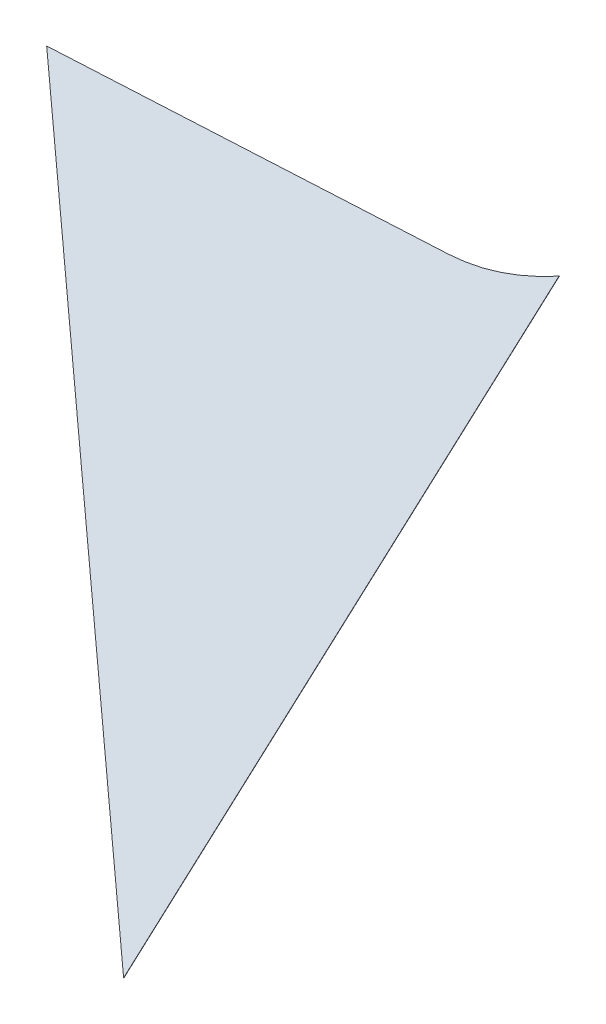
SolidWorks part; units mm, degrees
ref_plane "Front Plane" through (0, 0, 0) normal (0, 0, 1) x (1, 0, 0)
ref_plane "Top Plane" through (0, 0, 0) normal (0, 1, 0) x (1, 0, 0)
ref_plane "Right Plane" through (0, 0, 0) normal (1, 0, 0) x (0, 0, -1)
sketch "Tube Reference" plane through (-105.1856, -357.6475, -787.5535) normal (0.0455, -0.7723, -0.6336) x (0.9985, 0.0553, 0.0043)
  line L0 (-198.1326, 66.9643) -> (198.1326, 66.9643) construction
  line L1 (235, 58.2094) -> (235, 577.288) construction
  line L2 (-198.1326, 66.9643) -> (198.1326, 66.9643)
  line L3 (235, 58.2094) -> (235, 577.288)
  ellipse E0 centre (198.1326, -15.0318) end of major axis (280.1326, -15.0318) minor radius 81.9961 (263.9946, 33.8145) -> (198.1326, 66.9643) ccw construction
  ellipse E1 centre (198.1326, -15.0318) end of major axis (280.1326, -15.0318) minor radius 81.9961 (263.9946, 33.8145) -> (198.1326, 66.9643) ccw
sketch "Sketch2" plane through (-105.1856, -357.6475, -787.5535) normal (0.0455, -0.7723, -0.6336) x (0.9985, 0.0553, 0.0043)
  line L0 (-198.1326, 66.9643) -> (198.1326, 66.9643) construction
  line L1 (235, 58.2094) -> (235, 577.288) construction
  line L2 (40.5227, 66.9643) -> (198.1326, 66.9643)
  line L3 (235, 58.2094) -> (235, 287.1081)
  line L4 (235, 58.2094) -> (235, 577.288) construction
  line L5 (235, 287.1081) -> (40.5227, 66.9643)
  ellipse E0 centre (198.1326, -15.0318) end of major axis (280.1326, -15.0318) minor radius 81.9961 (263.9946, 33.8145) -> (198.1326, 66.9643) ccw construction
  ellipse E1 centre (198.1326, -15.0318) end of major axis (280.1326, -15.0318) minor radius 81.9961 (235, 58.2094) -> (198.1326, 66.9643) ccw
extrude "Boss-Extrude1" add sketch "Sketch2" along normal mid plane 0.1524
sketch "Sketch3" plane through (-105.1856, -357.6475, -787.5535) normal (0.0455, -0.7723, -0.6336) x (0.9985, 0.0553, 0.0043)
  point P0 (206.4576, 154.3059)
